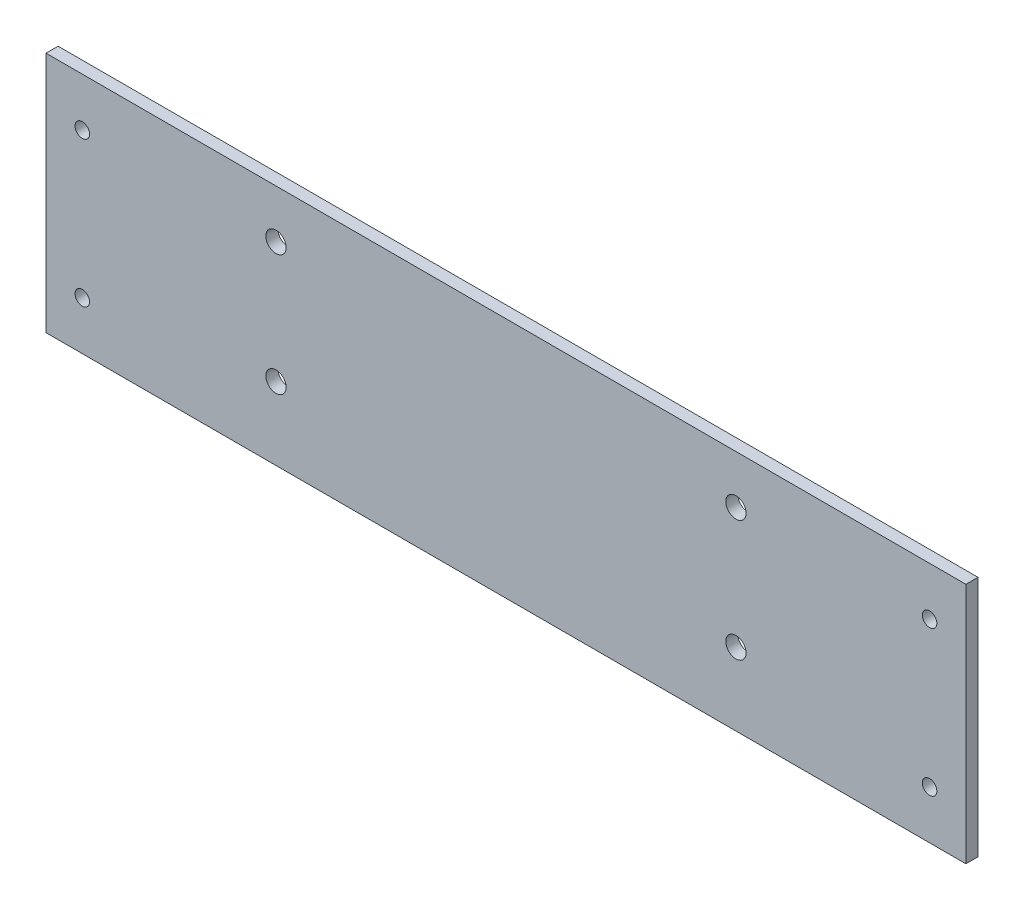
SolidWorks part; units mm, degrees
ref_plane "前视基准面" through (0, 0, 0) normal (0, 0, 1) x (1, 0, 0)
ref_plane "上视基准面" through (0, 0, 0) normal (0, 1, 0) x (1, 0, 0)
ref_plane "右视基准面" through (0, 0, 0) normal (1, 0, 0) x (0, 0, -1)
sketch "Sketch1" plane through (0, 0, 0) normal (0, 0, 1) x (1, 0, 0)
  line L0 (-129.2259, 81.6042) -> (-129.2259, -63.3958) construction
  line L1 (-129.2259, 44.0673) -> (60.7741, 44.0673)
  line L2 (-129.2259, 44.0673) -> (-129.2259, -5.9327)
  line L3 (-129.2259, -5.9327) -> (60.7741, -5.9327)
  line L4 (60.7741, 44.0673) -> (60.7741, -5.9327)
  line L5 (60.7741, 81.6042) -> (60.7741, -63.3958) construction
  dimension "D2" = 50
  dimension "D3" = 0
  dimension "D4" = 0
extrude "Boss-Extrude1" add sketch "Sketch1" along normal blind 2.5
sketch "Sketch2" plane through (0, 0, 2.5) normal (0, 0, 1) x (1, 0, 0)
  line L0 (-129.2259, 44.0673) -> (-129.2259, -5.9327) construction
  line L1 (60.7741, -5.9327) -> (60.7741, 44.0673) construction
  line L2 (60.7741, 44.0673) -> (-129.2259, 44.0673) construction
  line L3 (-129.2259, -5.9327) -> (60.7741, -5.9327) construction
  circle A0 centre (-121.7259, 34.0673) radius 1.5
  circle A1 centre (-121.7259, 4.0673) radius 1.5
  circle A2 centre (53.2741, 34.0673) radius 1.5
  circle A3 centre (53.2741, 4.0673) radius 1.5
  dimension "D1" = 3
  dimension "D2" = 3
  dimension "D3" = 3
  dimension "D4" = 3
  dimension "D5" = 7.5
  dimension "D6" = 7.5
  dimension "D8" = 7.5
  dimension "D9" = 10
  dimension "D10" = 10
  dimension "D11" = 10
  dimension "D12" = 10
  dimension "D7" = 7.5
extrude "Cut-Extrude1" cut sketch "Sketch2" against normal through all
sketch "Sketch3" plane through (0, 0, 2.5) normal (0, 0, 1) x (1, 0, 0)
  line L0 (60.7741, 44.0673) -> (-129.2259, 44.0673) construction
  line L1 (-129.2259, 44.0673) -> (-129.2259, -5.9327) construction
  circle A0 centre (-81.7259, 34.0673) radius 2.1
  circle A1 centre (13.2741, 34.0673) radius 2.1
  circle A2 centre (13.2741, 9.0673) radius 2.1
  circle A3 centre (-81.7259, 9.0673) radius 2.1
  dimension "D1" = 4.2
  dimension "D2" = 25
  dimension "D3" = 95
  dimension "D4" = 95
  dimension "D5" = 25
  dimension "D6" = 4.2
  dimension "D7" = 4.2
  dimension "D8" = 4.2
  dimension "D9" = 10
  dimension "D10" = 47.5
  dimension "D11" = 47.5
extrude "Cut-Extrude2" cut sketch "Sketch3" against normal through all
